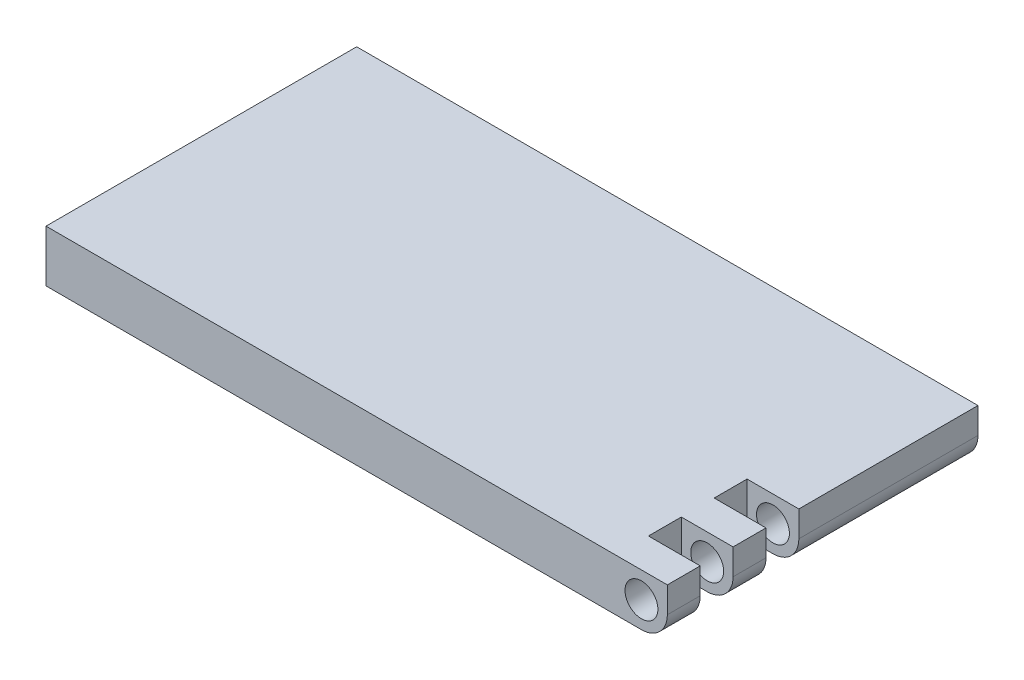
SolidWorks part; units mm, degrees
material "Plain Carbon Steel"
ref_plane "Front Plane" through (0, 0, 0) normal (0, 0, 1) x (1, 0, 0)
ref_plane "Top Plane" through (0, 0, 0) normal (0, 1, 0) x (1, 0, 0)
ref_plane "Right Plane" through (0, 0, 0) normal (1, 0, 0) x (0, 0, -1)
sketch "Sketch1" plane through (0, 0, 0) normal (0, 1, 0) x (1, 0, 0)
  line L1 (-60, -30) -> (60, -30)
  line L2 (-60, -30) -> (-60, 30)
  line L3 (-60, 30) -> (60, 30)
  line L4 (60, -30) -> (60, 30)
  line L5 (-60, -30) -> (60, 30) construction
  line L6 (-60, 30) -> (60, -30) construction
  point P0 (0, 0)
  dimension "D1" = 120
  dimension "D2" = 60
extrude "Boss-Extrude1" add sketch "Sketch1" along normal blind 10
sketch "Sketch2" plane through (0, 0, 30) normal (0, 0, 1) x (1, 0, 0)
  line L8 (-60, 10) -> (60, 10) construction
  line L9 (-60, 0) -> (60, 0) construction
  line L10 (60, 10) -> (60, 0) construction
  circle A2 centre (55, 5) radius 3.175
  arc A3 (55, 10) -> (55, 0) centre (55, 5) cw construction
  point P11 (0, 0)
  dimension "D1" = 6.35
extrude "Cut-Extrude1" cut sketch "Sketch2" against normal through all
fillet "Fillet2" radius 5 1 edges at (60, 0, 0)
sketch "Sketch4" plane through (0, 10, 0) normal (0, 1, 0) x (1, 0, 0)
  line L0 (60, -30) -> (60, 30) construction
  line L1 (60, -23.65) -> (50, -23.65)
  line L2 (60, -23.65) -> (60, -17.3)
  line L3 (60, -17.3) -> (50, -17.3)
  line L4 (50, -23.65) -> (50, -17.3)
  line L5 (-60, -30) -> (60, -30) construction
  dimension "D1" = 10
  dimension "D2" = 6.35
  dimension "D3" = 6.35
extrude "Cut-Extrude2" cut sketch "Sketch4" against normal through all
pattern_linear "LPattern1" count 2 spacing 12.7 along (0, 0, -1) of "Cut-Extrude2"
